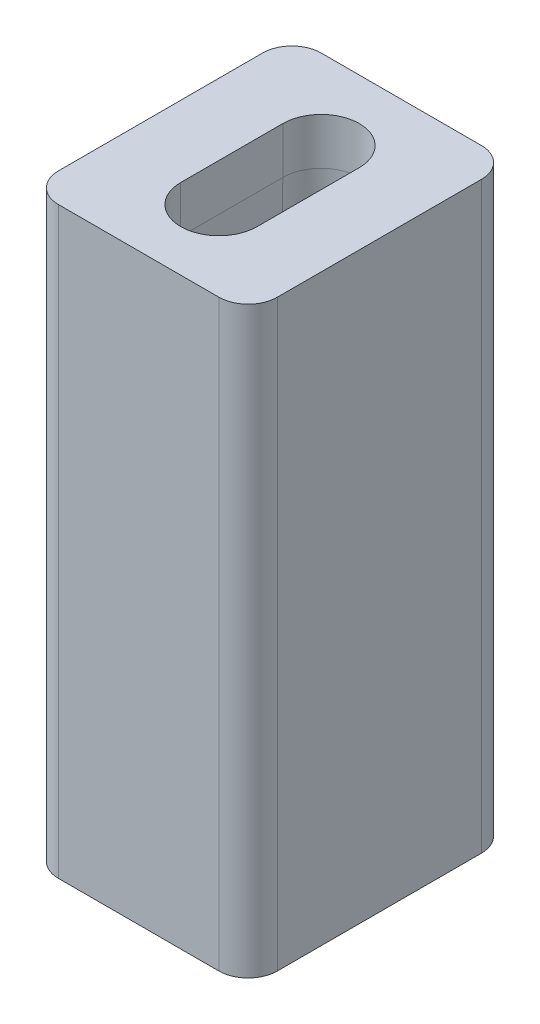
SolidWorks part; units mm, degrees
material "K110"
ref_plane "Front Plane" through (0, 0, 0) normal (0, 0, 1) x (1, 0, 0)
ref_plane "Top Plane" through (0, 0, 0) normal (0, 1, 0) x (1, 0, 0)
ref_plane "Right Plane" through (0, 0, 0) normal (1, 0, 0) x (0, 0, -1)
sketch "Sketch1" plane through (0, 0, 0) normal (0, 1, 0) x (1, 0, 0)
  line L3 (0, -3.5) -> (0, 3.5) construction
  line L4 (-2.62, -3.5) -> (-2.62, 3.5) construction
  line L5 (2.62, -3.5) -> (2.62, 3.5) construction
  line L6 (-5.5, -9) -> (5.5, -9)
  line L7 (-7.5, -7) -> (-7.5, 7)
  line L8 (-5.5, 9) -> (5.5, 9)
  line L9 (7.5, -7) -> (7.5, 7)
  line L10 (-7.5, -9) -> (7.5, 9) construction
  line L11 (-7.5, 9) -> (7.5, -9) construction
  arc A2 (-2.62, -3.5) -> (2.62, -3.5) centre (0, -3.5) ccw construction
  arc A3 (2.62, 3.5) -> (-2.62, 3.5) centre (0, 3.5) ccw construction
  arc A4 (-5.5, -9) -> (-7.5, -7) centre (-5.5, -7) cw
  arc A5 (5.5, -9) -> (7.5, -7) centre (5.5, -7) ccw
  arc A6 (5.5, 9) -> (7.5, 7) centre (5.5, 7) cw
  arc A7 (-7.5, 7) -> (-5.5, 9) centre (-5.5, 7) cw
  point P0 (0, 0)
  point P10 (0, 0)
  dimension "D1" = 7
  dimension "D3" = 2.62
  dimension "D5" = 2
  dimension "D2" = 18
  dimension "D4" = 15
extrude "Boss-Extrude1" add sketch "Sketch1" against normal blind 40
sketch "Sketch5" plane through (0, 0, 0) normal (0, 1, 0) x (1, 0, 0)
  line L0 (0, -3.5) -> (0, 3.5) construction
  line L1 (-2.62, -3.5) -> (-2.62, 3.5)
  line L2 (2.62, -3.5) -> (2.62, 3.5)
  arc A0 (-2.62, -3.5) -> (2.62, -3.5) centre (0, -3.5) ccw
  arc A1 (2.62, 3.5) -> (-2.62, 3.5) centre (0, 3.5) ccw
  point P4 (0, 0)
extrude "Cut-Extrude2" cut sketch "Sketch5" against normal up to next
sketch "Sketch7" plane through (0, 0, 0) normal (0, 0, 1) x (1, 0, 0)
  line L0 (2.62, -3.2) -> (3.2623, -40)
  line L1 (2.62, -40) -> (2.62, 0) construction
  line L2 (-5.5, -40) -> (5.5, -40) construction
  line L3 (3.2623, -40) -> (2.62, -40)
  line L4 (2.62, -40) -> (2.62, -3.2)
  line L5 (7.5, 0) -> (5.5, 0) construction
  dimension "D1" = 3.2
  dimension "D2" = 1
sketch "Sketch8" plane through (0, 0, 0) normal (0, 1, 0) x (1, 0, 0)
  line L0 (-2.62, 3.5) -> (-2.62, -3.5) construction
  line L1 (2.62, -3.5) -> (2.62, 3.5) construction
  line L2 (-2.62, 3.5) -> (-2.62, -3.5)
  line L3 (2.62, -3.5) -> (2.62, 3.5)
  arc A0 (2.62, 3.5) -> (-2.62, 3.5) centre (0, 3.5) ccw construction
  arc A1 (-2.62, -3.5) -> (2.62, -3.5) centre (0, -3.5) ccw construction
  arc A2 (2.62, 3.5) -> (-2.62, 3.5) centre (0, 3.5) ccw
  arc A3 (-2.62, -3.5) -> (2.62, -3.5) centre (0, -3.5) ccw
sweep "Cut-Sweep1" cut profiles "Sketch7" path "Sketch8"
hole_wizard "M3 Tapped Hole1" positions "Sketch11" profile "Sketch10" tap size "M3" standard "ISO"
sketch "Sketch11" plane through (0, -40, 0) normal (0, -1, 0) x (-1, 0, 0)
  line L0 (-5.5, 9) -> (5.5, 9) construction
  line L1 (-7.5, -7) -> (-7.5, 7) construction
  line L4 (7.5, 7) -> (7.5, -7) construction
  line L5 (5.5, -9) -> (-5.5, -9) construction
  point P0 (-5, 6.5)
  point P2 (5, -6.5)
  point P15 (9.7704, -1.6963)
  dimension "D1" = 2.5
  dimension "D2" = 2.5
  dimension "D3" = 2.5
  dimension "D4" = 2.5
sketch "Sketch10" plane through (5, -40, -6.5) normal (1, 0, 0) x (0, 0, -1)
  line L0 (0, 0) -> (0, 9.2511)
  line L1 (0, 9.2511) -> (1.25, 8.5)
  line L2 (1.25, 8.5) -> (1.25, 0.275)
  line L3 (1.25, 0.275) -> (1.525, 0)
  line L5 (1.525, 0) -> (0, 0)
  line L6 (-1.25, 0.275) -> (-1.525, 0) construction
  line L10 (0, 9.2511) -> (-1.25, 8.5) construction
  line L11 (0, -6.35) -> (0, 107.95) construction
  dimension "Tap Drill Dia." = 2.5
  dimension "Tap Drill Depth" = 8.5
  dimension "Near C'Sink Dia." = 3.05
  dimension "Near C'Sink Angle" = 90
  dimension "Drill Angle" = 118
cosmetic thread "Hole Thread1"
cosmetic thread "Hole Thread2"
